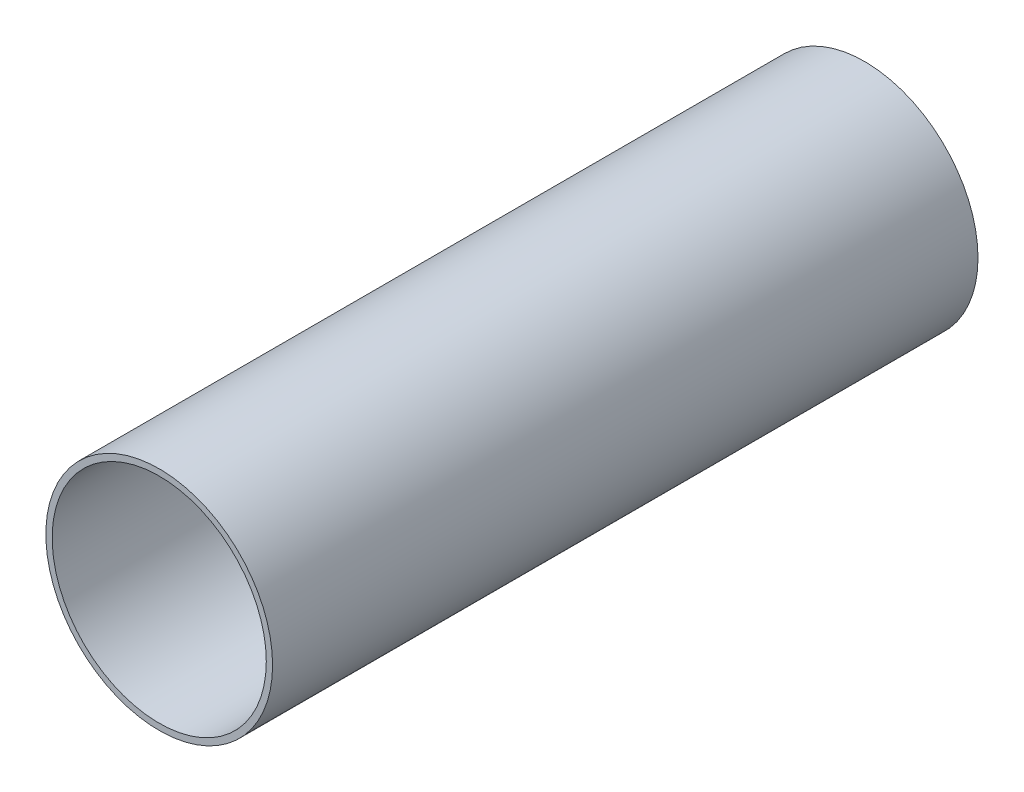
SolidWorks part; units mm, degrees
ref_plane "Front Plane" through (0, 0, 0) normal (0, 0, 1) x (1, 0, 0)
ref_plane "Top Plane" through (0, 0, 0) normal (0, 1, 0) x (1, 0, 0)
ref_plane "Right Plane" through (0, 0, 0) normal (1, 0, 0) x (0, 0, -1)
sketch "Sketch1" plane through (0, 0, 0) normal (0, 0, 1) x (1, 0, 0)
  circle A0 centre (0, 0) radius 28.575
  circle A1 centre (0, 0) radius 26.9875
  dimension "D1" = 57.15
  dimension "D2" = 53.975
extrude "Boss-Extrude1" add sketch "Sketch1" along normal blind 177.8
equation "\"D1@Sketch1\"=2+1/4"
equation "\"D2@Sketch1\"=2+1/8"
